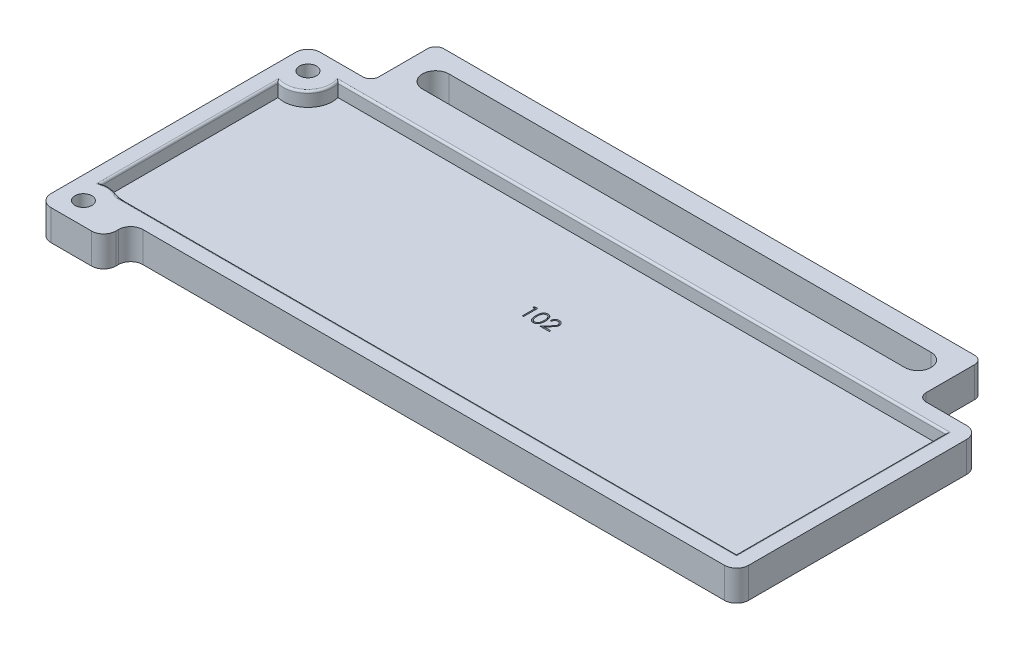
SolidWorks part; units mm, degrees
ref_plane "Front Plane" through (0, 0, 0) normal (0, 0, 1) x (1, 0, 0)
ref_plane "Top Plane" through (0, 0, 0) normal (0, 1, 0) x (1, 0, 0)
ref_plane "Right Plane" through (0, 0, 0) normal (1, 0, 0) x (0, 0, -1)
sketch "Sketch1" plane through (0, 0, 0) normal (0, 1, 0) x (1, 0, 0)
  line L0 (0, 0) -> (0, 55.4) construction
  line L4 (-2.5, 60.9) -> (156.975, 60.9)
  line L5 (-5.5, 57.9) -> (-5.5, -2.5)
  line L11 (7.5, -5.5) -> (-2.5, -5.5)
  line L12 (159.975, 57.9) -> (159.975, 4.15)
  line L13 (156.975, 1.15) -> (13.5, 1.15)
  line L14 (10.5, -1.85) -> (10.5, -2.5)
  circle A0 centre (0, 55.4) radius 2.09
  circle A1 centre (0, 0) radius 2.09
  arc A8 (-2.5, -5.5) -> (-5.5, -2.5) centre (-2.5, -2.5) cw
  arc A9 (-5.5, 57.9) -> (-2.5, 60.9) centre (-2.5, 57.9) cw
  arc A10 (159.975, 4.15) -> (156.975, 1.15) centre (156.975, 4.15) cw
  arc A11 (159.975, 57.9) -> (156.975, 60.9) centre (156.975, 57.9) ccw
  arc A12 (10.5, -2.5) -> (7.5, -5.5) centre (7.5, -2.5) cw
  arc A13 (10.5, -1.85) -> (13.5, 1.15) centre (13.5, -1.85) cw
  point P24 (10.5, 1.15)
  point P32 (-5.5, -5.5)
  point P35 (-5.5, 60.9)
  dimension "D2" = 4.18
  dimension "D11" = 59.75
  dimension "D7" = 3
  dimension "D8" = 3
  dimension "D9" = 3
  dimension "D1" = 55.4
  dimension "D3" = 5.5
  dimension "D4" = 165.475
  dimension "D5" = 5.5
  dimension "D6" = 5.5
  dimension "D12" = 16
extrude "Boss-Extrude1" add sketch "Sketch1" along normal blind 7.5
extrude "Boss-Extrude2" add sketch "Sketch1<2>" along normal blind 2 contours A1 | A0 region at (0, 0, -55.4) region at (0, 0, 0)
sketch "Sketch1<2>" plane through (0, 0, 0) normal (0, 1, 0) x (1, 0, 0) same geometry as "Sketch1"
shell "Shell1" thickness 4 removed face at (54.9917, 7.5, -18.85)
sketch "Sketch4" plane through (0, 7.5, 0) normal (0, 1, 0) x (1, 0, 0)
  line L0 (13.5, 5.15) -> (3.2505, 5.15)
  line L1 (6.5088, -1.5) -> (5.9024, -1.5)
  arc A0 (5.9024, -1.5) -> (-1.5, 5.9024) centre (0, 0) ccw construction
  arc A1 (13.5, 5.15) -> (6.5088, -1.5) centre (13.5, -1.85) ccw
  arc A2 (5.9024, -1.5) -> (3.2505, 5.15) centre (0, 0) ccw
extrude "Boss-Extrude4" add sketch "Sketch4" against normal up to surface (3.5 mm away)
fillet "Fillet1" radius 0.5 6 edges at (0.9527, 7.5, -6.015) (-1.5, 7.5, -27.7) (4.3063, 7.5, -51.0937) (80.9387, 7.5, -56.9) (155.975, 7.5, -31.025) (79.6127, 7.5, -5.15)
sketch "Sketch3" plane through (0, 0, 0) normal (0, 1, 0) x (1, 0, 0)
  line L0 (156.975, 60.9) -> (-2.5, 60.9) construction
  line L1 (10, 60.9) -> (144.975, 60.9)
  line L2 (10, 60.9) -> (10, 76.9)
  line L3 (10, 76.9) -> (144.975, 76.9)
  line L4 (144.975, 60.9) -> (144.975, 76.9)
  line L6 (18, 68.9) -> (136.975, 68.9) construction
  line L7 (18, 72.15) -> (136.975, 72.15)
  line L8 (18, 65.65) -> (136.975, 65.65)
  line L9 (159.975, 4.15) -> (159.975, 57.9) construction
  arc A0 (-1.5, 49.4976) -> (5.9024, 56.9) centre (0, 55.4) ccw construction
  arc A1 (18, 72.15) -> (18, 65.65) centre (18, 68.9) ccw
  arc A2 (136.975, 65.65) -> (136.975, 72.15) centre (136.975, 68.9) ccw
  point P13 (77.4875, 68.9)
  point P21 (14.75, 68.9)
  point P22 (140.225, 68.9)
  dimension "D2" = 10
  dimension "D6" = 4.75
  dimension "D1" = 16
  dimension "D3" = 15
  dimension "D4" = 8
  dimension "D5" = 6.5
  dimension "D7" = 4.75
extrude "Boss-Extrude3" add sketch "Sketch3" along normal up to surface (7.5 mm away) up to face at (53.2808, 7.5, -29.6296)
fillet "Fillet3" radius 2 4 edges at (144.975, 3.75, -76.9) (144.975, 3.75, -60.9) (10, 3.75, -76.9) (10, 3.75, -60.9)
fillet "Fillet4" radius 10.5 2 edges at (3.2208, 7.303, -5.0477) (3.2505, 5.5, -5.15)
sketch "Sketch5" plane through (0, 4, 0) normal (0, 1, 0) x (1, 0, 0)
  text T0 "102"
extrude "Cut-Extrude1" cut sketch "Sketch5" against normal blind 1
